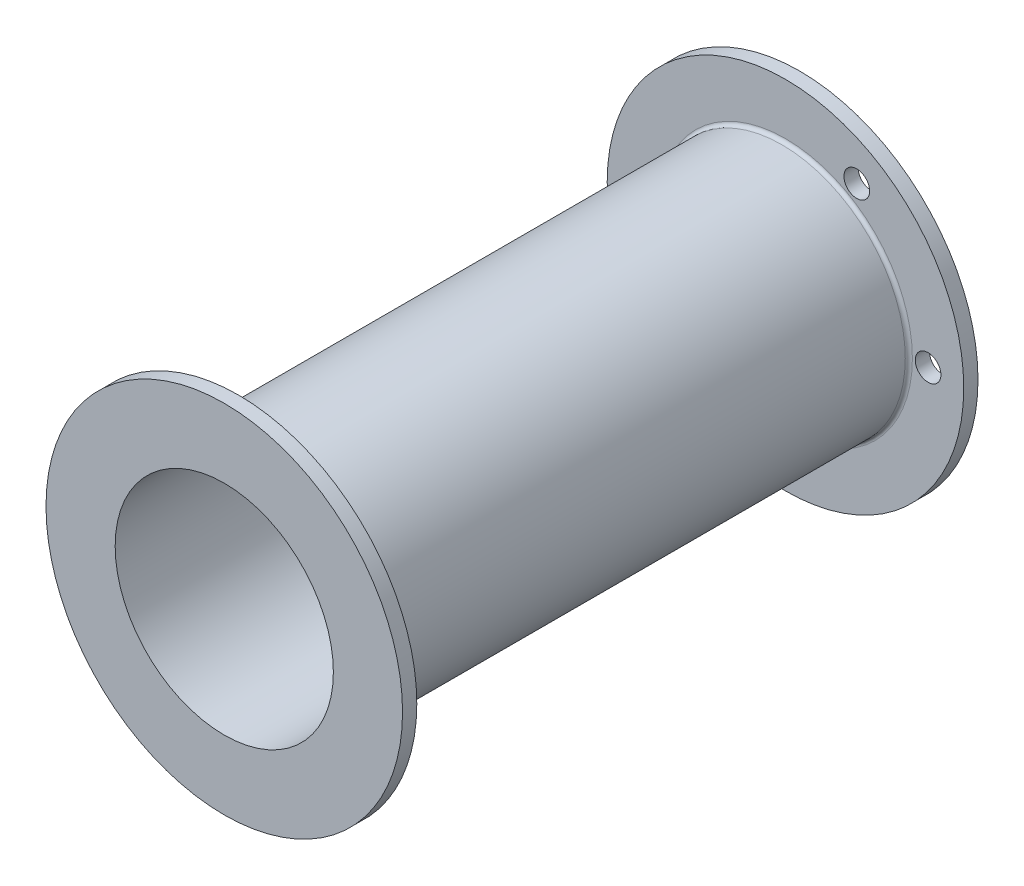
SolidWorks part; units mm, degrees
material "1060 Alloy"
ref_plane "Front Plane" through (0, 0, 0) normal (0, 0, 1) x (1, 0, 0)
ref_plane "Top Plane" through (0, 0, 0) normal (0, 1, 0) x (1, 0, 0)
ref_plane "Right Plane" through (0, 0, 0) normal (1, 0, 0) x (0, 0, -1)
sketch "Sketch1" plane through (0, 0, 0) normal (0, 0, 1) x (1, 0, 0)
  circle A0 centre (0, 0) radius 7.65
  circle A1 centre (0, 0) radius 8.65
  dimension "D1" = 15.3
  dimension "D2" = 17.3
extrude "Boss-Extrude1" add sketch "Sketch1" along normal blind 39.35
sketch "Sketch2" plane through (0, 0, 0) normal (0, 0, -1) x (-1, 0, 0)
  circle A0 centre (0, 0) radius 12.5
  circle A2 centre (0, 0) radius 7.65
  dimension "D1" = 25
extrude "Boss-Extrude2" add sketch "Sketch2" along normal blind 1
hole_wizard "M1.6 Clearance Hole1" positions "Sketch10" profile "Sketch11" hole size "M1.6" standard "ISO"
sketch "Sketch10" plane through (0, 0, 0) normal (0, 0, 1) x (1, 0, 0)
  point P0 (-10, 0)
  dimension "D1" = 10
sketch "Sketch11" plane through (-10, 0, 0) normal (1, 0, 0) x (0, -1, 0)
  line L0 (0, 0) -> (0, 5.5408)
  line L1 (0, 5.5408) -> (0.9, 5)
  line L2 (0.9, 5) -> (0.9, 0)
  line L5 (0.9, 0) -> (0, 0)
  line L10 (0, 5.5408) -> (-0.9, 5) construction
  line L11 (0, -6.35) -> (0, 107.95) construction
  dimension "Hole Dia." = 1.8
  dimension "Hole Depth" = 5
  dimension "Drill Angle" = 118
pattern_circular "CirPattern1" count 6 over 360 about axis through (0, 0, 0) along (0, 0, -1) skipping 1, 4 of "M1.6 Clearance Hole1"
fillet "Fillet1" radius 0.25 1 edges at (8.65, 0, 0)
ref_plane "Plane1" through (0, 0, 19.175) normal (0, 0, 1) x (1, 0, 0)
mirror "Mirror1" about plane through (0, 0, 19.175) normal (0, 0, 1) of "Boss-Extrude2"
